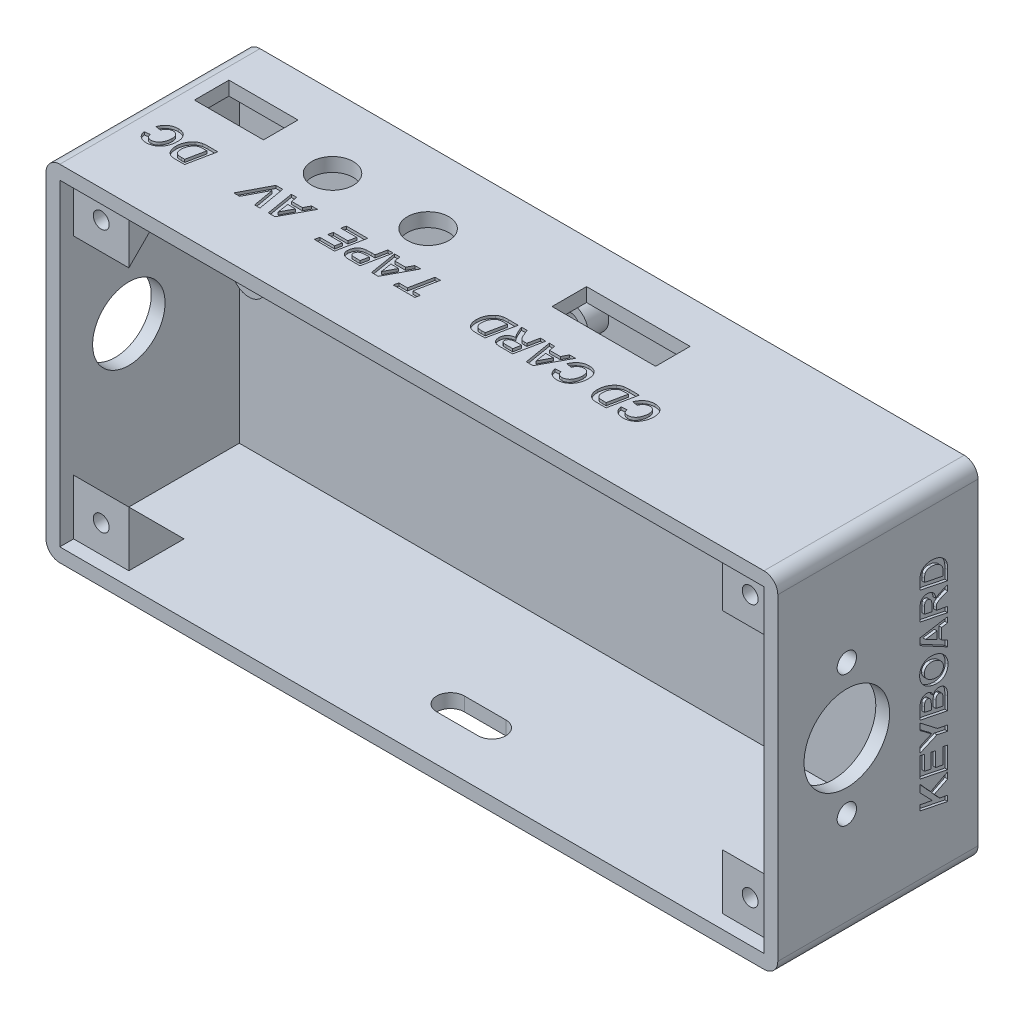
SolidWorks part; units mm, degrees
material "ABS"
ref_plane "Спереди" through (0, 0, 0) normal (0, 0, 1) x (1, 0, 0)
ref_plane "Сверху" through (0, 0, 0) normal (0, 1, 0) x (1, 0, 0)
ref_plane "Справа" through (0, 0, 0) normal (1, 0, 0) x (0, 0, -1)
sketch "Эскиз1" plane through (0, 0, 0) normal (0, 0, 1) x (1, 0, 0)
  line L1 (-53, -25) -> (53, -25)
  line L2 (-53, -25) -> (-53, 25)
  line L3 (-53, 25) -> (53, 25)
  line L4 (53, -25) -> (53, 25)
  line L5 (-53, -25) -> (53, 25) construction
  line L6 (-53, 25) -> (53, -25) construction
  point P0 (0, 0)
  dimension "D1" = 106
  dimension "D2" = 50
extrude "CaseBody" add sketch "Эскиз1" along normal blind 3
sketch "Эскиз2" plane through (0, 0, 3) normal (0, 0, 1) x (1, 0, 0)
  line L0 (53, 25) -> (-53, 25) construction
  line L1 (-51, -23) -> (51, -23)
  line L2 (-51, -23) -> (-51, 23)
  line L3 (-51, 23) -> (51, 23)
  line L4 (51, -23) -> (51, 23)
  line L5 (-51, -23) -> (51, 23) construction
  line L6 (-51, 23) -> (51, -23) construction
  line L7 (53, -25) -> (53, 25) construction
  line L9 (-53, -25) -> (53, -25)
  line L10 (-53, -25) -> (-53, 25)
  line L11 (-53, 25) -> (53, 25)
  line L12 (53, -25) -> (53, 25)
  line L13 (-53, -25) -> (53, 25) construction
  line L14 (-53, 25) -> (53, -25) construction
  point P0 (0, 0)
  point P10 (0, 0)
  dimension "D1" = 2
  dimension "D2" = 2
extrude "CaseBody2" add sketch "Эскиз2" along normal blind 26
sketch "Эскиз3" plane through (0, 0, 3) normal (0, 0, 1) x (1, 0, 0)
  line L0 (51, 23) -> (-51, 23) construction
  line L1 (-46.625, 1.53) -> (46.625, 1.53) construction
  line L2 (-46.625, 1.53) -> (-46.625, 19.18) construction
  line L3 (-46.625, 19.18) -> (46.625, 19.18) construction
  line L4 (46.625, 1.53) -> (46.625, 19.18) construction
  line L5 (-46.625, 1.53) -> (46.625, 19.18) construction
  line L6 (-46.625, 19.18) -> (46.625, 1.53) construction
  circle A0 centre (-46.625, 1.53) radius 2.5
  circle A1 centre (46.625, 1.53) radius 2.5
  circle A2 centre (0.005, 19.18) radius 2.5
  point P0 (0, 0)
  point P13 (0, 10.355)
  dimension "D4" = 5
  dimension "D1" = 93.25
  dimension "D2" = 17.65
  dimension "D3" = 46.63
  dimension "D5" = 3.82
extrude "SizifXXSFix" add sketch "Эскиз3" along normal blind 3
sketch "Эскиз4" plane through (0, 0, 6) normal (0, 0, 1) x (1, 0, 0)
  circle A0 centre (-46.625, 1.53) radius 1.2
  circle A1 centre (0.005, 19.18) radius 1.2
  circle A2 centre (46.625, 1.53) radius 1.2
  dimension "D1" = 2.4
extrude "Holes2_5" cut sketch "Эскиз4" against normal blind 5.6
sketch "Эскиз5" plane through (0, 25, 0) normal (0, 1, 0) x (1, 0, 0)
  line L1 (-49.3, -6.2) -> (-39.3, -6.2)
  line L2 (-49.3, -6.2) -> (-49.3, -11.2)
  line L3 (-49.3, -11.2) -> (-39.3, -11.2)
  line L4 (-39.3, -6.2) -> (-39.3, -11.2)
  line L5 (-49.3, -6.2) -> (-39.3, -11.2) construction
  line L6 (-49.3, -11.2) -> (-39.3, -6.2) construction
  line L7 (2.5, -6.2) -> (17.5, -6.2)
  line L8 (2.5, -6.2) -> (2.5, -11.2)
  line L9 (2.5, -11.2) -> (17.5, -11.2)
  line L10 (17.5, -6.2) -> (17.5, -11.2)
  line L11 (2.5, -6.2) -> (17.5, -11.2) construction
  line L12 (2.5, -11.2) -> (17.5, -6.2) construction
  line L13 (53, 0) -> (-53, 0) construction
  line L14 (-53, -29) -> (-53, 0) construction
  circle A0 centre (-30.1, -10.4) radius 3
  circle A1 centre (-16.25, -10.4) radius 3
  point P0 (-44.3, -8.7)
  point P9 (10, -8.7)
  dimension "D5" = 6
  dimension "D2" = 10
  dimension "D3" = 6.2
  dimension "D4" = 5
  dimension "D6" = 13.85
  dimension "D7" = 14.2
  dimension "D8" = 26.25
  dimension "D9" = 10.4
  dimension "D10" = 5
  dimension "D11" = 15
  dimension "D12" = 22.9
extrude "SizifXXS_Holes" cut sketch "Эскиз5" against normal up to next
sketch "Эскиз7" plane through (53, 0, 0) normal (1, 0, 0) x (0, 0, -1)
  line L0 (-20, 0) -> (-6.0564, 0) construction
  line L2 (0, -25) -> (0, 25) construction
  circle A0 centre (-19, 0) radius 6.2
  circle A1 centre (-19, -9.5) radius 1.4
  circle A2 centre (-19, 9.5) radius 1.4
  dimension "D1" = 12.4
  dimension "D4" = 2.8
  dimension "D2" = 19
  dimension "D3" = 19
extrude "PS2Hole" cut sketch "Эскиз7" against normal up to next
sketch "Эскиз8" plane through (51, 0, 0) normal (-1, 0, 0) x (0, 0, 1)
  line L0 (27, 23) -> (27, 15)
  line L1 (29, 23) -> (3, 23) construction
  line L2 (27, 15) -> (19, 23)
  line L3 (19, 23) -> (27, 23)
  line L4 (29, -23) -> (29, 23) construction
  dimension "D1" = 8
  dimension "D2" = 8
  dimension "D3" = 2
extrude "CaseTopFix" add sketch "Эскиз8" along normal blind 8
sketch "Эскиз9" plane through (0, 0, 27) normal (0, 0, 1) x (1, 0, 0)
  line L0 (43, 15) -> (43, 23) construction
  line L1 (43, 23) -> (51, 23) construction
  line L2 (43, 23) -> (43, 15) construction
  line L3 (43, 15) -> (51, 15) construction
  line L4 (51, 23) -> (51, 15) construction
  line L5 (43, 23) -> (51, 15) construction
  line L6 (43, 15) -> (51, 23) construction
  line L7 (43, 23) -> (51, 23) construction
  circle A0 centre (47, 19) radius 1.15
  point P0 (47, 19)
  dimension "D1" = 2.3
extrude "CaseTopHoles" cut sketch "Эскиз9" against normal up to next
mirror "CaseTopHoles1" about plane through (0, 0, 0) normal (0, 1, 0) of "CaseTopHoles", "CaseTopFix"
mirror "CaseTopHoles2" about plane through (0, 0, 0) normal (1, 0, 0) of "CaseTopHoles", "CaseTopHoles1", "CaseTopFix"
fillet "Fillet" radius 2 4 edges at (-53, 25, 14.5) (53, 25, 14.5) (53, -25, 14.5) (-53, -25, 14.5)
sketch "Эскиз10" plane through (0, 25, 0) normal (0, 1, 0) x (1, 0, 0)
  line L0 (51, 0) -> (-51, 0) construction
  line L1 (-53, -29) -> (-53, 0) construction
  text T0 "<r180>VA</r>" font "Times New Roman" height 4
  text T1 "<r180>EPAT</r>" font "Times New Roman" height 4
  text T2 "<r180>CD</r>" font "Times New Roman" height 4
  text T3 "<r180>DRAC DC</r>" font "Times New Roman" height 4
  dimension "D1" = 16
  dimension "D2" = 22.5962
  dimension "D3" = 11.2585
  dimension "D4" = 14.4528
  dimension "D5" = 21.8
extrude "InterfaceInfo" cut sketch "Эскиз10" against normal blind 0.4
sketch "Эскиз11" plane through (53, 0, 0) normal (1, 0, 0) x (0, 0, -1)
  line L0 (-4.4, -15.5) -> (-4.4, 15.5) construction
  line L1 (0, -23) -> (0, 23) construction
  text T0 "KEYBOARD" font "Arial" height 4
  point P0 (-4.4, 0)
  dimension "D1" = 4.4
  dimension "D2" = 31
extrude "PS2Info" cut sketch "Эскиз11" against normal blind 0.4
sketch "Эскиз12" plane through (0, 23, 0) normal (0, -1, 0) x (1, 0, 0)
  line L1 (-53, 0) -> (-53, 29) construction
  line L2 (-51, 0) -> (51, 0) construction
  text T0 "© Peter Ukhov 2023" font "Arial" height 6
  dimension "D1" = 16
  dimension "D2" = 14
sketch "Эскиз13" plane through (-53, 0, 0) normal (-1, 0, 0) x (0, 0, 1)
  line L1 (0, 23) -> (0, -23) construction
  circle A0 centre (19, 0) radius 5.25
  dimension "D1" = 10.5
  dimension "D2" = 19
extrude "ButtonHole" cut sketch "Эскиз13" against normal up to next
sketch "Эскиз14" plane through (-53, 0, 0) normal (-1, 0, 0) x (0, 0, 1)
  line L0 (6.2274, 10.1387) -> (6.2274, -12.1287) construction
  text T0 "POWER" font "Arial" height 4
extrude "ButtonInfo" cut sketch "Эскиз14" against normal blind 0.4
extrude "CopyLeft" cut sketch "Эскиз12" against normal blind 0.4
sketch "Эскиз15" plane through (0, -25, 0) normal (0, -1, 0) x (1, 0, 0)
  line L0 (-3, 20.4) -> (3, 20.4) construction
  line L1 (-3, 22.4) -> (3, 22.4)
  line L2 (-3, 18.4) -> (3, 18.4)
  line L3 (-51, 29) -> (51, 29) construction
  arc A0 (-3, 22.4) -> (-3, 18.4) centre (-3, 20.4) ccw
  arc A1 (3, 18.4) -> (3, 22.4) centre (3, 20.4) ccw
  point P2 (0, 20.4)
  point P7 (0, 0)
  dimension "D1" = 4
  dimension "D2" = 6
  dimension "D3" = 8.6
extrude "USBArduinoNano" cut sketch "Эскиз15" against normal up to next
equation "\"D1@Эскиз1\"=100+2*2+2"
equation "\"D5@Эскиз3\"=3.42+0.4"
equation "\"D2@Эскиз15\"=10-2-2"
